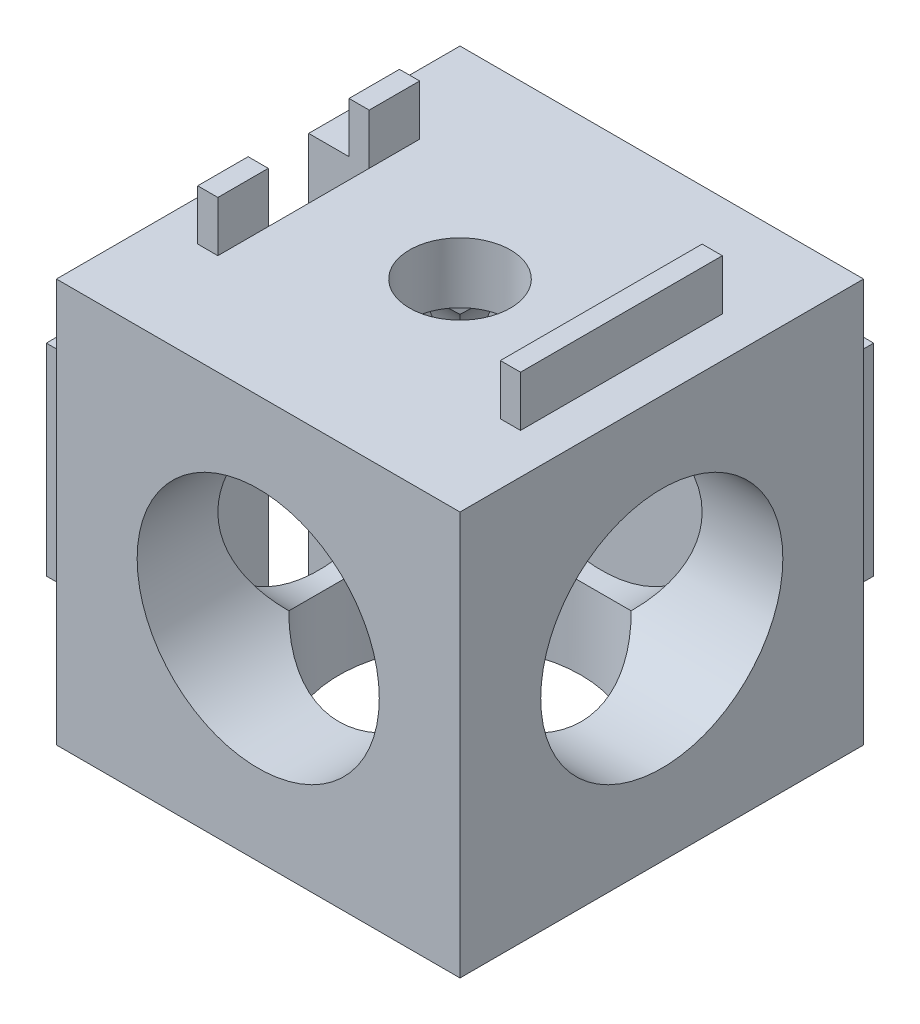
SolidWorks part; units mm, degrees
ref_plane "Front Plane" through (0, 0, 0) normal (0, 0, 1) x (1, 0, 0)
ref_plane "Top Plane" through (0, 0, 0) normal (0, 1, 0) x (1, 0, 0)
ref_plane "Right Plane" through (0, 0, 0) normal (1, 0, 0) x (0, 0, -1)
sketch "Sketch1" plane through (0, 0, 0) normal (0, 1, 0) x (1, 0, 0)
  line L0 (0, 7.5) -> (3, 7.5)
  line L1 (0, 0) -> (20, 0)
  line L2 (0, 0) -> (0, 7.5)
  line L3 (0, 20) -> (20, 20)
  line L4 (20, 0) -> (20, 20)
  line L5 (3, 7.5) -> (3, 12.5)
  line L6 (3, 12.5) -> (0, 12.5)
  line L7 (0, 12.5) -> (0, 20)
extrude "Boss-Extrude1" add sketch "Sketch1" along normal blind 20
sketch "Sketch2" plane through (0, 20, 0) normal (0, 1, 0) x (1, 0, 0)
  line L1 (2, 7.5) -> (3, 7.5)
  line L2 (2, 7.5) -> (2, 5)
  line L3 (2, 5) -> (3, 5)
  line L4 (3, 7.5) -> (3, 5)
  line L5 (2, 15) -> (3, 15)
  line L6 (2, 15) -> (2, 12.5)
  line L7 (2, 12.5) -> (3, 12.5)
  line L8 (3, 15) -> (3, 12.5)
  line L9 (17, 15) -> (18, 15)
  line L10 (17, 15) -> (17, 5)
  line L11 (17, 5) -> (18, 5)
  line L12 (18, 15) -> (18, 5)
  circle A0 centre (10, 10) radius 2.5
extrude "Boss-Extrude2" add sketch "Sketch2" along normal blind 2.5 contours L4 L2 L3 | L8 L5 L6 A0 | L12 L9 L10 L11 region at (2.5, 20, -6.25) region at (2.5, 20, -13.75) region at (17.5, 20, -10)
extrude "Cut-Extrude1" cut sketch "Sketch2<3>" against normal through all contours A0 region at (10, 20, -10)
sketch "Sketch2<3>" plane through (0, 20, 0) normal (0, 1, 0) x (1, 0, 0) same geometry as "Sketch2"
sketch "Sketch3" plane through (0, 0, 0) normal (-1, 0, 0) x (0, 0, 1)
  line L1 (-2, 15) -> (-3, 15)
  line L2 (-2, 15) -> (-2, 5)
  line L3 (-2, 5) -> (-3, 5)
  line L4 (-3, 15) -> (-3, 5)
  line L5 (-18, 15) -> (-17, 15)
  line L6 (-18, 15) -> (-18, 5)
  line L7 (-18, 5) -> (-17, 5)
  line L8 (-17, 15) -> (-17, 5)
extrude "Boss-Extrude3" add sketch "Sketch3" along normal blind 2.5
sketch "Sketch4" plane through (0, 0, -20) normal (0, 0, -1) x (-1, 0, 0)
  line L1 (-18, 15) -> (-17, 15)
  line L2 (-18, 15) -> (-18, 5)
  line L3 (-18, 5) -> (-17, 5)
  line L4 (-17, 15) -> (-17, 5)
  line L5 (-2, 15) -> (-3, 15)
  line L6 (-2, 15) -> (-2, 5)
  line L7 (-2, 5) -> (-3, 5)
  line L8 (-3, 15) -> (-3, 5)
  line L9 (-15, 3) -> (-5, 3)
  line L10 (-15, 3) -> (-15, 2)
  line L11 (-15, 2) -> (-5, 2)
  line L12 (-5, 3) -> (-5, 2)
  circle A0 centre (-10, 10) radius 2.5
extrude "Boss-Extrude4" add sketch "Sketch4" along normal blind 2.5 contours L4 L1 L2 L3 | L5 L8 L7 L6 | L12 L9 L10 L11 region at (17.5, 10, -20) region at (2.5, 10, -20) region at (10, 2.5, -20)
extrude "Cut-Extrude2" cut sketch "Sketch4<3>" against normal through all contours A0 region at (10, 10, -20)
sketch "Sketch4<3>" plane through (0, 0, -20) normal (0, 0, -1) x (-1, 0, 0) same geometry as "Sketch4"
sketch "Sketch5" plane through (20, 0, 0) normal (1, 0, 0) x (0, 0, -1)
  circle A0 centre (10, 10) radius 6
extrude "Cut-Extrude3" cut sketch "Sketch5" against normal blind 17
sketch "Sketch6" plane through (0, 0, 0) normal (0, 0, 1) x (1, 0, 0)
  circle A0 centre (10, 10) radius 6
extrude "Cut-Extrude4" cut sketch "Sketch6" against normal blind 17
sketch "Sketch7" plane through (0, 0, 0) normal (0, -1, 0) x (1, 0, 0)
  circle A0 centre (10, -10) radius 6
extrude "Cut-Extrude5" cut sketch "Sketch7" against normal blind 17
